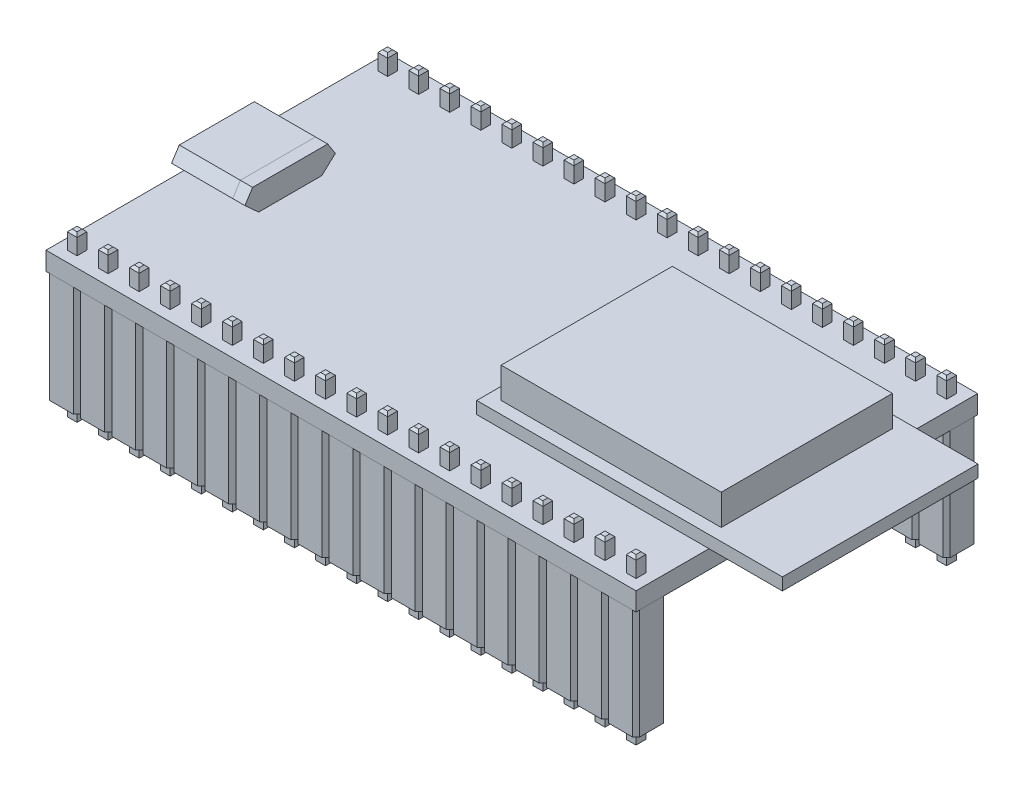
SolidWorks part; units mm, degrees
ref_plane "Plan de face" through (0, 0, 0) normal (0, 0, 1) x (1, 0, 0)
ref_plane "Plan de dessus" through (0, 0, 0) normal (0, 1, 0) x (1, 0, 0)
ref_plane "Plan de droite" through (0, 0, 0) normal (1, 0, 0) x (0, 0, -1)
sketch "Esquisse1" plane through (0, 0, 0) normal (0, 1, 0) x (1, 0, 0)
  line L1 (24.13, -13.97) -> (-24.13, -13.97)
  line L2 (24.13, -13.97) -> (24.13, 13.97)
  line L3 (24.13, 13.97) -> (-24.13, 13.97)
  line L4 (-24.13, -13.97) -> (-24.13, 13.97)
  line L5 (24.13, -13.97) -> (-24.13, 13.97) construction
  line L6 (24.13, 13.97) -> (-24.13, -13.97) construction
  point P0 (0, 0)
  dimension "D1" = 48.26
  dimension "D2" = 27.94
extrude "Boss.-Extru.1" add sketch "Esquisse1" along normal blind 1.5
sketch "Esquisse2" plane through (0, 1.5, 0) normal (0, 1, 0) x (1, 0, 0)
  line L0 (-24.13, 13.97) -> (-24.13, -13.97) construction
  line L1 (-23.26, -12.3) -> (-22.46, -12.3)
  line L2 (-23.26, -12.3) -> (-23.26, -13.1)
  line L3 (-23.26, -13.1) -> (-22.46, -13.1)
  line L4 (-22.46, -12.3) -> (-22.46, -13.1)
  line L5 (-23.26, -12.3) -> (-22.46, -13.1) construction
  line L6 (-23.26, -13.1) -> (-22.46, -12.3) construction
  line L7 (-24.13, -13.97) -> (24.13, -13.97) construction
  line L8 (-19.92, -12.3) -> (-19.92, -13.1)
  line L9 (-20.72, -13.1) -> (-19.92, -13.1)
  line L10 (-20.72, -12.3) -> (-20.72, -13.1)
  line L11 (-20.72, -12.3) -> (-19.92, -12.3)
  line L12 (-17.38, -12.3) -> (-17.38, -13.1)
  line L13 (-18.18, -13.1) -> (-17.38, -13.1)
  line L14 (-18.18, -12.3) -> (-18.18, -13.1)
  line L15 (-18.18, -12.3) -> (-17.38, -12.3)
  line L16 (-14.84, -12.3) -> (-14.84, -13.1)
  line L17 (-15.64, -13.1) -> (-14.84, -13.1)
  line L18 (-15.64, -12.3) -> (-15.64, -13.1)
  line L19 (-15.64, -12.3) -> (-14.84, -12.3)
  line L20 (-12.3, -12.3) -> (-12.3, -13.1)
  line L21 (-13.1, -13.1) -> (-12.3, -13.1)
  line L22 (-13.1, -12.3) -> (-13.1, -13.1)
  line L23 (-13.1, -12.3) -> (-12.3, -12.3)
  line L24 (-9.76, -12.3) -> (-9.76, -13.1)
  line L25 (-10.56, -13.1) -> (-9.76, -13.1)
  line L26 (-10.56, -12.3) -> (-10.56, -13.1)
  line L27 (-10.56, -12.3) -> (-9.76, -12.3)
  line L28 (-7.22, -12.3) -> (-7.22, -13.1)
  line L29 (-8.02, -13.1) -> (-7.22, -13.1)
  line L30 (-8.02, -12.3) -> (-8.02, -13.1)
  line L31 (-8.02, -12.3) -> (-7.22, -12.3)
  line L32 (-4.68, -12.3) -> (-4.68, -13.1)
  line L33 (-5.48, -13.1) -> (-4.68, -13.1)
  line L34 (-5.48, -12.3) -> (-5.48, -13.1)
  line L35 (-5.48, -12.3) -> (-4.68, -12.3)
  line L36 (-2.14, -12.3) -> (-2.14, -13.1)
  line L37 (-2.94, -13.1) -> (-2.14, -13.1)
  line L38 (-2.94, -12.3) -> (-2.94, -13.1)
  line L39 (-2.94, -12.3) -> (-2.14, -12.3)
  line L40 (0.4, -12.3) -> (0.4, -13.1)
  line L41 (-0.4, -13.1) -> (0.4, -13.1)
  line L42 (-0.4, -12.3) -> (-0.4, -13.1)
  line L43 (-0.4, -12.3) -> (0.4, -12.3)
  line L44 (2.94, -12.3) -> (2.94, -13.1)
  line L45 (2.14, -13.1) -> (2.94, -13.1)
  line L46 (2.14, -12.3) -> (2.14, -13.1)
  line L47 (2.14, -12.3) -> (2.94, -12.3)
  line L48 (5.48, -12.3) -> (5.48, -13.1)
  line L49 (4.68, -13.1) -> (5.48, -13.1)
  line L50 (4.68, -12.3) -> (4.68, -13.1)
  line L51 (4.68, -12.3) -> (5.48, -12.3)
  line L52 (8.02, -12.3) -> (8.02, -13.1)
  line L53 (7.22, -13.1) -> (8.02, -13.1)
  line L54 (7.22, -12.3) -> (7.22, -13.1)
  line L55 (7.22, -12.3) -> (8.02, -12.3)
  line L56 (10.56, -12.3) -> (10.56, -13.1)
  line L57 (9.76, -13.1) -> (10.56, -13.1)
  line L58 (9.76, -12.3) -> (9.76, -13.1)
  line L59 (9.76, -12.3) -> (10.56, -12.3)
  line L60 (13.1, -12.3) -> (13.1, -13.1)
  line L61 (12.3, -13.1) -> (13.1, -13.1)
  line L62 (12.3, -12.3) -> (12.3, -13.1)
  line L63 (12.3, -12.3) -> (13.1, -12.3)
  line L64 (15.64, -12.3) -> (15.64, -13.1)
  line L65 (14.84, -13.1) -> (15.64, -13.1)
  line L66 (14.84, -12.3) -> (14.84, -13.1)
  line L67 (14.84, -12.3) -> (15.64, -12.3)
  line L68 (18.18, -12.3) -> (18.18, -13.1)
  line L69 (17.38, -13.1) -> (18.18, -13.1)
  line L70 (17.38, -12.3) -> (17.38, -13.1)
  line L71 (17.38, -12.3) -> (18.18, -12.3)
  line L72 (20.72, -12.3) -> (20.72, -13.1)
  line L73 (19.92, -13.1) -> (20.72, -13.1)
  line L74 (19.92, -12.3) -> (19.92, -13.1)
  line L75 (19.92, -12.3) -> (20.72, -12.3)
  line L76 (23.26, -12.3) -> (23.26, -13.1)
  line L77 (22.46, -13.1) -> (23.26, -13.1)
  line L78 (22.46, -12.3) -> (22.46, -13.1)
  line L79 (22.46, -12.3) -> (23.26, -12.3)
  line L80 (-19.92, 13.1) -> (-19.92, 12.3)
  line L81 (-20.72, 12.3) -> (-19.92, 12.3)
  line L82 (-20.72, 13.1) -> (-20.72, 12.3)
  line L83 (-20.72, 13.1) -> (-19.92, 13.1)
  line L84 (-17.38, 13.1) -> (-17.38, 12.3)
  line L85 (-18.18, 12.3) -> (-17.38, 12.3)
  line L86 (-18.18, 13.1) -> (-18.18, 12.3)
  line L87 (-18.18, 13.1) -> (-17.38, 13.1)
  line L88 (-14.84, 13.1) -> (-14.84, 12.3)
  line L89 (-15.64, 12.3) -> (-14.84, 12.3)
  line L90 (-15.64, 13.1) -> (-15.64, 12.3)
  line L91 (-15.64, 13.1) -> (-14.84, 13.1)
  line L92 (-12.3, 13.1) -> (-12.3, 12.3)
  line L93 (-13.1, 12.3) -> (-12.3, 12.3)
  line L94 (-13.1, 13.1) -> (-13.1, 12.3)
  line L95 (-13.1, 13.1) -> (-12.3, 13.1)
  line L96 (-9.76, 13.1) -> (-9.76, 12.3)
  line L97 (-10.56, 12.3) -> (-9.76, 12.3)
  line L98 (-10.56, 13.1) -> (-10.56, 12.3)
  line L99 (-10.56, 13.1) -> (-9.76, 13.1)
  line L100 (-7.22, 13.1) -> (-7.22, 12.3)
  line L101 (-8.02, 12.3) -> (-7.22, 12.3)
  line L102 (-8.02, 13.1) -> (-8.02, 12.3)
  line L103 (-8.02, 13.1) -> (-7.22, 13.1)
  line L104 (-4.68, 13.1) -> (-4.68, 12.3)
  line L105 (-5.48, 12.3) -> (-4.68, 12.3)
  line L106 (-5.48, 13.1) -> (-5.48, 12.3)
  line L107 (-5.48, 13.1) -> (-4.68, 13.1)
  line L108 (-2.14, 13.1) -> (-2.14, 12.3)
  line L109 (-2.94, 12.3) -> (-2.14, 12.3)
  line L110 (-2.94, 13.1) -> (-2.94, 12.3)
  line L111 (-2.94, 13.1) -> (-2.14, 13.1)
  line L112 (0.4, 13.1) -> (0.4, 12.3)
  line L113 (-0.4, 12.3) -> (0.4, 12.3)
  line L114 (-0.4, 13.1) -> (-0.4, 12.3)
  line L115 (-0.4, 13.1) -> (0.4, 13.1)
  line L116 (2.94, 13.1) -> (2.94, 12.3)
  line L117 (2.14, 12.3) -> (2.94, 12.3)
  line L118 (2.14, 13.1) -> (2.14, 12.3)
  line L119 (2.14, 13.1) -> (2.94, 13.1)
  line L120 (5.48, 13.1) -> (5.48, 12.3)
  line L121 (4.68, 12.3) -> (5.48, 12.3)
  line L122 (4.68, 13.1) -> (4.68, 12.3)
  line L123 (4.68, 13.1) -> (5.48, 13.1)
  line L124 (8.02, 13.1) -> (8.02, 12.3)
  line L125 (7.22, 12.3) -> (8.02, 12.3)
  line L126 (7.22, 13.1) -> (7.22, 12.3)
  line L127 (7.22, 13.1) -> (8.02, 13.1)
  line L128 (10.56, 13.1) -> (10.56, 12.3)
  line L129 (9.76, 12.3) -> (10.56, 12.3)
  line L130 (9.76, 13.1) -> (9.76, 12.3)
  line L131 (9.76, 13.1) -> (10.56, 13.1)
  line L132 (13.1, 13.1) -> (13.1, 12.3)
  line L133 (12.3, 12.3) -> (13.1, 12.3)
  line L134 (12.3, 13.1) -> (12.3, 12.3)
  line L135 (12.3, 13.1) -> (13.1, 13.1)
  line L136 (15.64, 13.1) -> (15.64, 12.3)
  line L137 (14.84, 12.3) -> (15.64, 12.3)
  line L138 (14.84, 13.1) -> (14.84, 12.3)
  line L139 (14.84, 13.1) -> (15.64, 13.1)
  line L140 (18.18, 13.1) -> (18.18, 12.3)
  line L141 (17.38, 12.3) -> (18.18, 12.3)
  line L142 (17.38, 13.1) -> (17.38, 12.3)
  line L143 (17.38, 13.1) -> (18.18, 13.1)
  line L144 (20.72, 13.1) -> (20.72, 12.3)
  line L145 (19.92, 12.3) -> (20.72, 12.3)
  line L146 (19.92, 13.1) -> (19.92, 12.3)
  line L147 (19.92, 13.1) -> (20.72, 13.1)
  line L148 (23.26, 13.1) -> (23.26, 12.3)
  line L149 (22.46, 12.3) -> (23.26, 12.3)
  line L150 (22.46, 13.1) -> (22.46, 12.3)
  line L151 (22.46, 13.1) -> (23.26, 13.1)
  line L152 (-22.46, 13.1) -> (-22.46, 12.3)
  line L153 (-23.26, 12.3) -> (-22.46, 12.3)
  line L154 (-23.26, 13.1) -> (-23.26, 12.3)
  line L155 (-23.26, 13.1) -> (-22.46, 13.1)
  point P0 (-22.86, -12.7)
  dimension "D1" = 0.8
  dimension "D2" = 0.8
  dimension "D3" = 1.27
  dimension "D4" = 1.27
  dimension "D5" = 19
  dimension "D6" = 2
extrude "Boss.-Extru.2" add sketch "Esquisse2" along normal blind 1.5 and the other way blind 12
chamfer "Chanfrein1" distance 0.2 angle 45 304 edges at (19.92, 3, -12.7) (20.32, 3, -13.1) (20.72, 3, -12.7) (20.32, 3, -12.3) (-10.56, 3, -12.7) (-10.16, 3, -13.1) (-9.76, 3, -12.7) (-10.16, 3, -12.3) (-22.46, -10.5, -12.7) (-22.86, -10.5, -13.1) (-23.26, -10.5, -12.7) (-22.86, -10.5, -12.3) (-19.92, -10.5, -12.7) (-20.32, -10.5, -13.1) (-20.72, -10.5, -12.7) (-20.32, -10.5, -12.3) (-17.38, -10.5, -12.7) (-17.78, -10.5, -13.1) (-18.18, -10.5, -12.7) (-17.78, -10.5, -12.3) (-14.84, -10.5, -12.7) (-15.24, -10.5, -13.1) (-15.64, -10.5, -12.7) (-15.24, -10.5, -12.3) (-12.3, -10.5, -12.7) (-12.7, -10.5, -13.1) (-13.1, -10.5, -12.7) (-12.7, -10.5, -12.3) (-9.76, -10.5, -12.7) (-10.16, -10.5, -13.1) (-10.56, -10.5, -12.7) (-10.16, -10.5, -12.3) (-7.22, -10.5, -12.7) (-7.62, -10.5, -13.1) (-8.02, -10.5, -12.7) (-7.62, -10.5, -12.3) (-4.68, -10.5, -12.7) (-5.08, -10.5, -13.1) (-5.48, -10.5, -12.7) (-5.08, -10.5, -12.3) (-2.14, -10.5, -12.7) (-2.54, -10.5, -13.1) (-2.94, -10.5, -12.7) (-2.54, -10.5, -12.3) (0.4, -10.5, -12.7) (0, -10.5, -13.1) (-0.4, -10.5, -12.7) (0, -10.5, -12.3) (2.94, -10.5, -12.7) (2.54, -10.5, -13.1) (2.14, -10.5, -12.7) (2.54, -10.5, -12.3) (5.48, -10.5, -12.7) (5.08, -10.5, -13.1) (4.68, -10.5, -12.7) (5.08, -10.5, -12.3) (8.02, -10.5, -12.7) (7.62, -10.5, -13.1) (7.22, -10.5, -12.7) (7.62, -10.5, -12.3) (10.56, -10.5, -12.7) (10.16, -10.5, -13.1) (9.76, -10.5, -12.7) (10.16, -10.5, -12.3) (13.1, -10.5, -12.7) (12.7, -10.5, -13.1) (12.3, -10.5, -12.7) (12.7, -10.5, -12.3) (15.64, -10.5, -12.7) (15.24, -10.5, -13.1) (14.84, -10.5, -12.7) (15.24, -10.5, -12.3) (20.72, -10.5, -12.7) (20.32, -10.5, -13.1) (19.92, -10.5, -12.7) (20.32, -10.5, -12.3) (23.26, -10.5, -12.7) (22.86, -10.5, -13.1) (22.46, -10.5, -12.7) (22.86, -10.5, -12.3) (23.26, -10.5, 12.7) (22.86, -10.5, 12.3) (22.46, -10.5, 12.7) (22.86, -10.5, 13.1) (20.72, -10.5, 12.7) (20.32, -10.5, 12.3) (19.92, -10.5, 12.7) (20.32, -10.5, 13.1) (18.18, -10.5, 12.7) (17.78, -10.5, 12.3) (17.38, -10.5, 12.7) (17.78, -10.5, 13.1) (15.64, -10.5, 12.7) (15.24, -10.5, 12.3) (14.84, -10.5, 12.7) (15.24, -10.5, 13.1) (13.1, -10.5, 12.7) (12.7, -10.5, 12.3) (12.3, -10.5, 12.7) (12.7, -10.5, 13.1) (10.56, -10.5, 12.7) (10.16, -10.5, 12.3) (9.76, -10.5, 12.7) (10.16, -10.5, 13.1) (8.02, -10.5, 12.7) (7.62, -10.5, 12.3) (7.22, -10.5, 12.7) (7.62, -10.5, 13.1) (5.48, -10.5, 12.7) (5.08, -10.5, 12.3) (4.68, -10.5, 12.7) (5.08, -10.5, 13.1) (2.94, -10.5, 12.7) (2.54, -10.5, 12.3) (2.14, -10.5, 12.7) (2.54, -10.5, 13.1) (0.4, -10.5, 12.7) (0, -10.5, 12.3) (-0.4, -10.5, 12.7) (0, -10.5, 13.1) (-2.14, -10.5, 12.7) (-2.54, -10.5, 12.3) (-2.94, -10.5, 12.7) (-2.54, -10.5, 13.1) (-4.68, -10.5, 12.7) (-5.08, -10.5, 12.3) (-5.48, -10.5, 12.7) (-5.08, -10.5, 13.1) (-7.22, -10.5, 12.7) (-7.62, -10.5, 12.3) (-8.02, -10.5, 12.7) (-7.62, -10.5, 13.1) (-12.3, -10.5, 12.7) (-12.7, -10.5, 12.3) (-13.1, -10.5, 12.7) (-12.7, -10.5, 13.1) (-9.76, -10.5, 12.7) (-10.16, -10.5, 12.3) (-10.56, -10.5, 12.7) (-10.16, -10.5, 13.1) (-14.84, -10.5, 12.7) (-15.24, -10.5, 12.3) (-15.64, -10.5, 12.7) (-15.24, -10.5, 13.1) (-17.38, -10.5, 12.7) (-17.78, -10.5, 12.3) (-18.18, -10.5, 12.7) (-17.78, -10.5, 13.1) (-19.92, -10.5, 12.7) (-20.32, -10.5, 12.3) (-20.72, -10.5, 12.7) (-20.32, -10.5, 13.1) (-22.86, -10.5, 12.3) (-23.26, -10.5, 12.7) (-22.86, -10.5, 13.1) (-22.46, -10.5, 12.7) (18.18, -10.5, -12.7) (17.78, -10.5, -13.1) (17.38, -10.5, -12.7) (17.78, -10.5, -12.3) (22.46, 3, -12.7) (22.86, 3, -13.1) (23.26, 3, -12.7) (22.86, 3, -12.3) (17.38, 3, -12.7) (17.78, 3, -13.1) (18.18, 3, -12.7) (17.78, 3, -12.3) (14.84, 3, -12.7) (15.24, 3, -13.1) (15.64, 3, -12.7) (15.24, 3, -12.3) (12.3, 3, -12.7) (12.7, 3, -13.1) (13.1, 3, -12.7) (12.7, 3, -12.3) (9.76, 3, -12.7) (10.16, 3, -13.1) (10.56, 3, -12.7) (10.16, 3, -12.3) (7.22, 3, -12.7) (7.62, 3, -13.1) (8.02, 3, -12.7) (7.62, 3, -12.3) (4.68, 3, -12.7) (5.08, 3, -13.1) (5.48, 3, -12.7) (5.08, 3, -12.3) (2.14, 3, -12.7) (2.54, 3, -13.1) (2.94, 3, -12.7) (2.54, 3, -12.3) (-0.4, 3, -12.7) (0, 3, -13.1) (0.4, 3, -12.7) (0, 3, -12.3) (-2.94, 3, -12.7) (-2.54, 3, -13.1) (-2.14, 3, -12.7) (-2.54, 3, -12.3) (22.46, 3, 12.7) (22.86, 3, 12.3) (23.26, 3, 12.7) (22.86, 3, 13.1) (19.92, 3, 12.7) (20.32, 3, 12.3) (20.72, 3, 12.7) (20.32, 3, 13.1) (17.38, 3, 12.7) (17.78, 3, 12.3) (18.18, 3, 12.7) (17.78, 3, 13.1) (14.84, 3, 12.7) (15.24, 3, 12.3) (15.64, 3, 12.7) (15.24, 3, 13.1) (12.3, 3, 12.7) (12.7, 3, 12.3) (13.1, 3, 12.7) (12.7, 3, 13.1) (9.76, 3, 12.7) (10.16, 3, 12.3) (10.56, 3, 12.7) (10.16, 3, 13.1) (7.22, 3, 12.7) (7.62, 3, 12.3) (8.02, 3, 12.7) (7.62, 3, 13.1) (4.68, 3, 12.7) (5.08, 3, 12.3) (5.48, 3, 12.7) (5.08, 3, 13.1) (-0.4, 3, 12.7) (0, 3, 12.3) (0.4, 3, 12.7) (0, 3, 13.1) (2.14, 3, 12.7) (2.54, 3, 12.3) (2.94, 3, 12.7) (2.54, 3, 13.1) (-2.94, 3, 12.7) (-2.54, 3, 12.3) (-2.14, 3, 12.7) (-2.54, 3, 13.1) (-5.48, 3, 12.7) (-5.08, 3, 12.3) (-4.68, 3, 12.7) (-5.08, 3, 13.1) (-8.02, 3, 12.7) (-7.62, 3, 12.3) (-7.22, 3, 12.7) (-7.62, 3, 13.1) (-10.56, 3, 12.7) (-10.16, 3, 12.3) (-9.76, 3, 12.7) (-10.16, 3, 13.1) (-13.1, 3, 12.7) (-12.7, 3, 12.3) (-12.3, 3, 12.7) (-12.7, 3, 13.1) (-15.64, 3, 12.7) (-15.24, 3, 12.3) (-14.84, 3, 12.7) (-15.24, 3, 13.1) (-18.18, 3, 12.7) (-17.78, 3, 12.3) (-17.38, 3, 12.7) (-17.78, 3, 13.1) (-20.72, 3, 12.7) (-20.32, 3, 12.3) (-19.92, 3, 12.7) (-20.32, 3, 13.1) (-22.86, 3, 13.1) (-23.26, 3, 12.7) (-22.86, 3, 12.3) (-22.46, 3, 12.7) (-5.48, 3, -12.7) (-5.08, 3, -13.1) (-4.68, 3, -12.7) (-5.08, 3, -12.3) (-8.02, 3, -12.7) (-7.62, 3, -13.1) (-7.22, 3, -12.7) (-7.62, 3, -12.3) (-13.1, 3, -12.7) (-12.7, 3, -13.1) (-12.3, 3, -12.7) (-12.7, 3, -12.3) (-15.64, 3, -12.7) (-15.24, 3, -13.1) (-14.84, 3, -12.7) (-15.24, 3, -12.3) (-18.18, 3, -12.7) (-17.78, 3, -13.1) (-17.38, 3, -12.7) (-17.78, 3, -12.3) (-20.72, 3, -12.7) (-20.32, 3, -13.1) (-19.92, 3, -12.7) (-20.32, 3, -12.3) (-23.26, 3, -12.7) (-22.86, 3, -13.1) (-22.46, 3, -12.7) (-22.86, 3, -12.3)
sketch "Esquisse4" plane through (0, 0, 0) normal (0, -1, 0) x (1, 0, 0)
  line L0 (-24.13, 13.97) -> (24.13, 13.97) construction
  line L1 (-21.89, 13.97) -> (-23.83, 13.97)
  line L2 (-21.59, 13.67) -> (-21.59, 11.73)
  line L3 (-21.89, 11.43) -> (-23.83, 11.43)
  line L4 (-24.13, 13.67) -> (-24.13, 11.73)
  line L5 (-24.13, -13.97) -> (-24.13, 13.97) construction
  line L6 (-23.83, 13.97) -> (-24.13, 13.67)
  line L7 (-24.13, 11.73) -> (-23.83, 11.43)
  line L8 (-21.59, 11.73) -> (-21.89, 11.43)
  line L9 (-21.89, 13.97) -> (-21.59, 13.67)
  point P0 (-21.59, 13.97)
  point P1 (-24.13, 11.43)
  point P2 (-21.59, 11.43)
  point P3 (-24.13, 13.97)
  dimension "D1" = 2.54
  dimension "D2" = 2.54
extrude "Boss.-Extru.3" add sketch "Esquisse4" along normal blind 9
pattern_linear "Répétition linéaire1" count 19 spacing 2.54 along (1, 0, 0) count 2 spacing 25.4 along (0, 0, -1) of "Boss.-Extru.3"
sketch "Esquisse5" plane through (-24.13, 0, 0) normal (-1, 0, 0) x (0, 0, 1)
  line L0 (0, 1.5) -> (0, 5.3573) construction
  line L1 (-2.5775, 1.5) -> (2.5775, 1.5)
  line L2 (-13.97, 1.5) -> (13.97, 1.5) construction
  line L3 (2.5775, 1.5) -> (3.7, 2.522)
  line L4 (3.7, 2.522) -> (3.0699, 3.5)
  line L5 (3.0699, 3.5) -> (-3.0699, 3.5)
  line L6 (-3.7, 2.522) -> (-3.0699, 3.5)
  line L7 (-2.5775, 1.5) -> (-3.7, 2.522)
  line L15 (-2.5001, 1.7) -> (2.5001, 1.7)
  line L16 (2.5001, 1.7) -> (3.4402, 2.556)
  line L17 (3.4402, 2.556) -> (2.9609, 3.3)
  line L18 (2.9609, 3.3) -> (-2.9609, 3.3)
  line L19 (-3.4402, 2.556) -> (-2.9609, 3.3)
  line L20 (-2.5001, 1.7) -> (-3.4402, 2.556)
  point P9 (0, 3.5)
  dimension "D1" = 0.978
  dimension "D2" = 3.7
  dimension "D4" = 0.2
extrude "Boss.-Extru.4" add sketch "Esquisse5" against normal blind 5 separate body
sketch "Esquisse6" plane through (-19.13, 0, 0) normal (1, 0, 0) x (0, 0, -1)
  line L0 (-3.0699, 3.5) -> (3.0699, 3.5)
  line L1 (3.0699, 3.5) -> (3.7, 2.522)
  line L2 (3.7, 2.522) -> (2.5775, 1.5)
  line L3 (2.5775, 1.5) -> (-2.5775, 1.5)
  line L4 (-2.5775, 1.5) -> (-3.7, 2.522)
  line L5 (-3.7, 2.522) -> (-3.0699, 3.5)
  point P4 (0, 0)
extrude "Boss.-Extru.5" add sketch "Esquisse6" along normal blind 1
sketch "Esquisse7" plane through (0, 1.5, 0) normal (0, 1, 0) x (1, 0, 0)
  line L0 (24.13, -13.97) -> (24.13, 13.97) construction
  line L1 (5.13, -8) -> (30.13, -8)
  line L2 (5.13, -8) -> (5.13, 8)
  line L3 (5.13, 8) -> (30.13, 8)
  line L4 (30.13, -8) -> (30.13, 8)
  dimension "D1" = 16
  dimension "D2" = 8
  dimension "D3" = 6
  dimension "D4" = 19
extrude "Boss.-Extru.6" add sketch "Esquisse7" along normal blind 1
sketch "Esquisse8" plane through (0, 2.5, 0) normal (0, 1, 0) x (1, 0, 0)
  line L0 (24.13, -13.97) -> (24.13, -8) construction
  line L1 (6.13, -7) -> (24.13, -7)
  line L2 (6.13, -7) -> (6.13, 7)
  line L3 (6.13, 7) -> (24.13, 7)
  line L4 (24.13, -7) -> (24.13, 7)
  line L5 (5.13, -8) -> (30.13, -8) construction
  line L6 (5.13, 8) -> (5.13, -8) construction
  line L7 (30.13, 8) -> (5.13, 8) construction
  dimension "D1" = 1
  dimension "D2" = 1
  dimension "D3" = 1
extrude "Boss.-Extru.7" add sketch "Esquisse8" along normal blind 2.5
equation "\"D1@Esquisse1\"=19*2.54"
equation "\"D2@Esquisse1\"=11*2.54"
equation "\"D3@Esquisse2\"=2.54/2"
